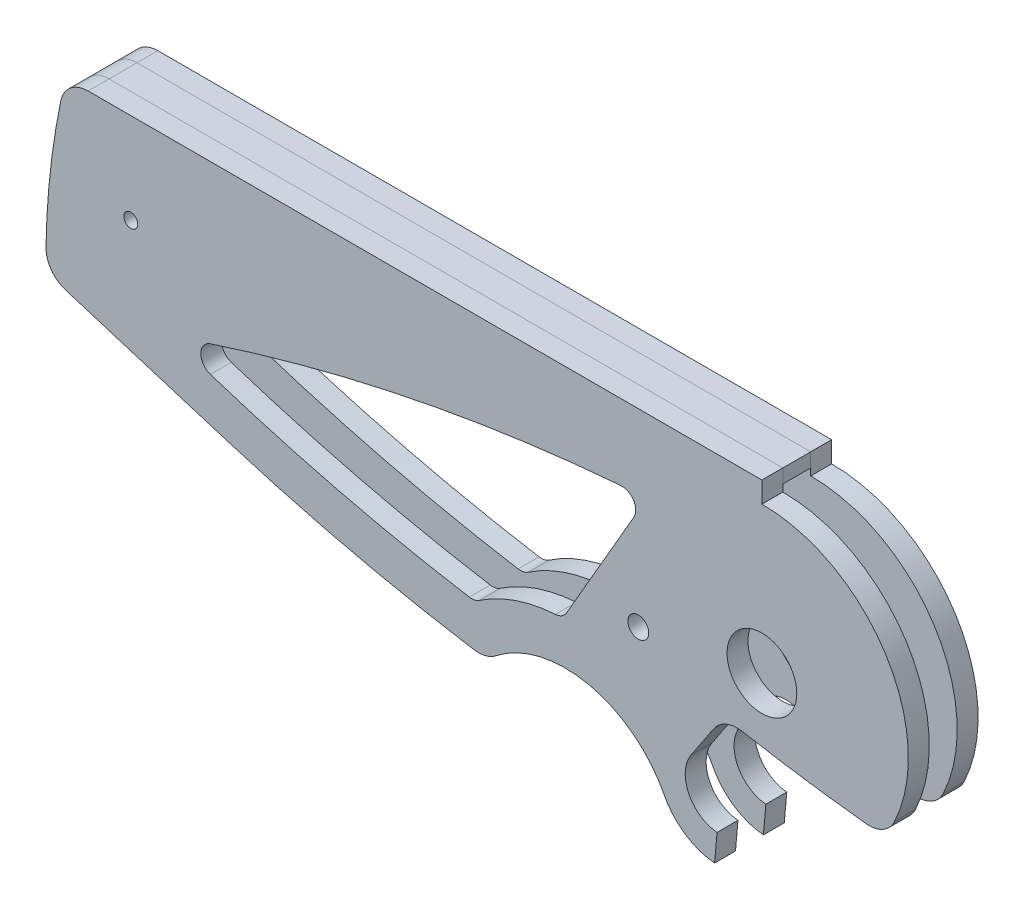
SolidWorks part; units mm, degrees
material "Obyčejná uhlíková ocel"
ref_plane "Přední rovina" through (0, 0, 0) normal (0, 0, 1) x (1, 0, 0)
ref_plane "Horní rovina" through (0, 0, 0) normal (0, 1, 0) x (1, 0, 0)
ref_plane "Pravá rovina" through (0, 0, 0) normal (1, 0, 0) x (0, 0, -1)
sketch "Skica15" plane through (0, 0, 0) normal (0, 0, 1) x (1, 0, 0)
  line L0 (0, 10) -> (0, -10)
  line L1 (0, 0) -> (-50, 0) construction
  line L2 (-1.7365, -9.8481) -> (1.7365, 9.8481)
  line L3 (0, 0) -> (49.2404, -8.6824) construction
  arc A0 (-50, 0) -> (0, 10) centre (0, -120) cw
  arc A1 (-50, 0) -> (0, -10) centre (0, 120) ccw
  arc A2 (1.7365, 9.8481) -> (49.2404, -8.6824) centre (-20.8378, -118.1769) cw
  arc A3 (-1.7365, -9.8481) -> (49.2404, -8.6824) centre (20.8378, 118.1769) ccw
  circle A4 centre (0, 0) radius 10
  dimension "D2" = 130
  dimension "D1" = 20
  dimension "D3" = 50
  dimension "D4" = 10
ref_plane "Rovina2" through (0, 0, 1) normal (0, 0, 1) x (1, 0, 0)
sketch "Skica1" plane through (0, 0, 1) normal (0, 0, 1) x (1, 0, 0)
  line L1 (-3.4519, -5.1731) -> (-5.0795, -7.6124)
  line L2 (0, 0) -> (-59.5409, 0) construction
  line L3 (-3, -9) -> (-3, -17.0212) construction
  line L4 (-3.2179, -11.4905) -> (-3.3922, -13.4829)
  line L5 (-49.9157, -1.1721) -> (-38.4483, -4.7076)
  line L6 (0, 10.5) -> (0, 12)
  line L7 (0, 12) -> (-48.3078, 12)
  circle A0 centre (0, 0) radius 2.5
  arc A1 (9.5026, -4.4665) -> (0, 10.5) centre (0, 0) ccw
  arc A2 (7.478, -5.6042) -> (-1.4305, -4.3154) centre (20.8378, 118.1769) cw
  arc A3 (-5.0795, -7.6124) -> (-3.2179, -11.4905) centre (-3, -9) ccw
  arc A4 (-7, -11.0616) -> (-3.3922, -13.4829) centre (-3, -9) ccw
  arc A5 (7.478, -5.6042) -> (9.5026, -4.4665) centre (7.6926, -3.6157) ccw
  arc A6 (-50.2663, 10.4054) -> (-51.3262, 0.7691) centre (0, 0) ccw
  arc A7 (-1.7365, -9.8481) -> (49.2404, -8.6824) centre (20.8378, 118.1769) ccw construction
  arc A8 (-7, -11.0616) -> (-19.0746, -8.4525) centre (-14.1111, -14.7265) ccw
  arc A9 (-51.3262, 0.7691) -> (-49.9157, -1.1721) centre (-49.3265, 0.7391) ccw
  arc A10 (-20.6316, -8.8588) -> (-38.4483, -4.7076) centre (0, 120) cw
  circle A11 centre (-50, 0) radius 1 construction
  arc A12 (-20.6316, -8.8588) -> (-19.0746, -8.4525) centre (-20.3154, -6.8839) ccw
  arc A13 (-50, 0) -> (0, -10) centre (0, 120) ccw construction
  arc A14 (-1.4305, -4.3154) -> (-3.4519, -5.1731) centre (-1.7882, -6.2832) ccw
  arc A15 (-48.3078, 12) -> (-50.2663, 10.4054) centre (-48.3078, 10) ccw
  point P34 (-19.7017, -9.0042)
  dimension "D1" = 5
  dimension "D2" = 10.5
  dimension "D3" = 2
  dimension "D4" = 5
  dimension "D5" = 3
  dimension "D6" = 9
  dimension "D7" = 2
  dimension "D10" = 2
  dimension "D11" = 2
  dimension "D13" = 2
  dimension "D14" = 12
  dimension "D12" = 2
  dimension "D9" = 0.5
  dimension "D16" = 8
  dimension "D17" = 1.5
  dimension "D19" = 2
  dimension "D15" = 2
  dimension "D8" = 5
  dimension "D18" = 7
extrude "Přidat vysunutím1" add sketch "Skica1" along normal blind 1.5
sketch "Skica2" plane through (0, 0, 0) normal (0, 0, 1) x (1, 0, 0)
  line L0 (-8.8633, -1.5628) -> (0, 0) construction
  line L2 (0, 0) -> (-50, 0) construction
  circle A0 centre (-8.8633, -1.5628) radius 0.75
  circle A1 centre (-45.2466, 5.5) radius 0.5
  dimension "D3" = 1.5
  dimension "D5" = 1
  dimension "D8" = 5.5
  dimension "D1" = 10
  dimension "D2" = 9
  dimension "D7" = 45.2466
sketch "Skica14" plane through (0, 0, 0) normal (0, 0, 1) x (1, 0, 0)
  line L0 (-14.001, -3.2504) -> (-9.1805, 5.0988)
  line L1 (0, 0) -> (-50, 0) construction
  arc A0 (-39.5409, -1.2137) -> (-20.9819, -5.7617) centre (0, 120) ccw
  arc A1 (-39.5422, 0.6873) -> (-10.1263, 6.5956) centre (0, -120) cw
  arc A2 (-38.4483, -4.7076) -> (-20.6316, -8.8588) centre (0, 120) ccw construction
  circle A3 centre (0, 0) radius 10 construction
  arc A4 (-39.5422, 0.6873) -> (-39.5409, -1.2137) centre (-39.2308, -0.263) ccw
  arc A5 (-20.2585, -5.6046) -> (-20.9819, -5.7617) centre (-20.8174, -4.7753) cw
  arc A6 (-9.1805, 5.0988) -> (-10.1263, 6.5956) centre (-10.0466, 5.5988) ccw
  arc A7 (0, 10) -> (-50, 0) centre (0, -120) ccw construction
  arc A8 (-20.2585, -5.6046) -> (-14.804, -3.7484) centre (-14.1111, -14.7265) cw
  arc A10 (-14.804, -3.7484) -> (-14.001, -3.2504) centre (-14.867, -2.7504) ccw
  arc A11 (-38.4483, -4.7076) -> (-20.6316, -8.8588) centre (0, 120) ccw construction
  arc A13 (-7, -11.0616) -> (-19.0746, -8.4525) centre (-14.1111, -14.7265) ccw construction
  dimension "D2" = 3
  dimension "D3" = 2
  dimension "D4" = 3
  dimension "D5" = 3
  dimension "D6" = 0.5
  dimension "D1" = 60
extrude "Odebrat vysunutím3" cut sketch "Skica14" along normal through all
extrude "Odebrat vysunutím2" cut sketch "Skica2" along normal through all
sketch "Skica16" plane through (0, 0, 0) normal (0, 0, -1) x (-1, 0, 0)
  line L0 (0, 12) -> (48.3078, 12) construction
  line L1 (0, 10.5) -> (0, 12) construction
  line L2 (0, 12) -> (48.3078, 12)
  line L3 (0, 11) -> (0, 12)
  arc A0 (51.3262, 0.7691) -> (50.2663, 10.4054) centre (0, 0) ccw construction
  arc A1 (49.9157, -1.1721) -> (51.3262, 0.7691) centre (49.3265, 0.7391) ccw construction
  arc A2 (50.2663, 10.4054) -> (48.3078, 12) centre (48.3078, 10) ccw construction
  arc A3 (51.3262, 0.7691) -> (50.2663, 10.4054) centre (0, 0) ccw
  arc A4 (51.3156, 0.531) -> (51.3262, 0.7691) centre (49.3265, 0.7391) ccw
  arc A5 (50.2663, 10.4054) -> (48.3078, 12) centre (48.3078, 10) ccw
  arc A13 (50.3846, 0.9231) -> (0, 11) centre (0, -120) ccw
  arc A14 (51.3156, 0.531) -> (0, 11) centre (0, -120) ccw
  dimension "D1" = 1
extrude "Přidat vysunutím2" add sketch "Skica16" along normal mid plane 2 separate body
mirror "Zrcadlit1" about plane through (0, 0, 0) normal (0, 0, 1) of bodies 119
